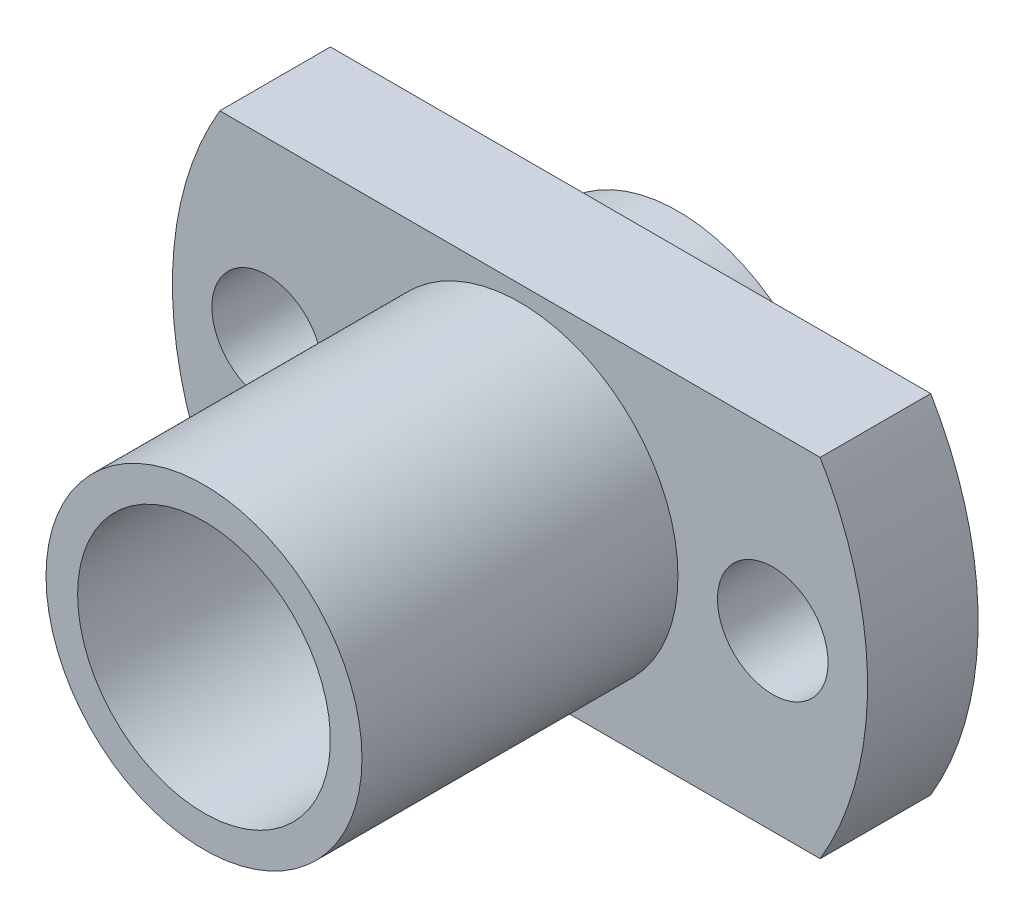
SolidWorks part; units mm, degrees
ref_plane "前视基准面" through (0, 0, 0) normal (0, 0, 1) x (1, 0, 0)
ref_plane "上视基准面" through (0, 0, 0) normal (0, 1, 0) x (1, 0, 0)
ref_plane "右视基准面" through (0, 0, 0) normal (1, 0, 0) x (0, 0, -1)
sketch "草图1" plane through (0, 0, 0) normal (0, 0, 1) x (1, 0, 0)
  line L1 (-9.5, -5.5) -> (9.5, -5.5)
  line L3 (-9.5, 5.5) -> (9.5, 5.5)
  arc A0 (-9.5, -5.5) -> (-9.5, 5.5) centre (-0.1667, 0) cw
  arc A1 (9.5, -5.5) -> (9.5, 5.5) centre (0.1667, 0) ccw
  circle A2 centre (8, 0) radius 1.75
  circle A3 centre (-8, 0) radius 1.75
  point P0 (0, 0)
  point P6 (0, 0)
extrude "凸台-拉伸1" add sketch "草图1" along normal blind 3.5
sketch "草图2" plane through (0, 0, 0) normal (0, 0, -1) x (-1, 0, 0)
  circle A0 centre (0, 0) radius 5
  circle A1 centre (0, 0) radius 4
extrude "凸台-拉伸2" add sketch "草图2" along normal blind 1.5 and the other way blind 13.5
sketch "草图3" plane through (0, 0, 0) normal (0, 0, -1) x (-1, 0, 0)
  point P0 (0, 0)
  circle M1 centre (0, 0) radius 4
extrude "切除-拉伸1" cut sketch "草图3" against normal blind 78.5 contours M1 region at (0, 0, 0)
